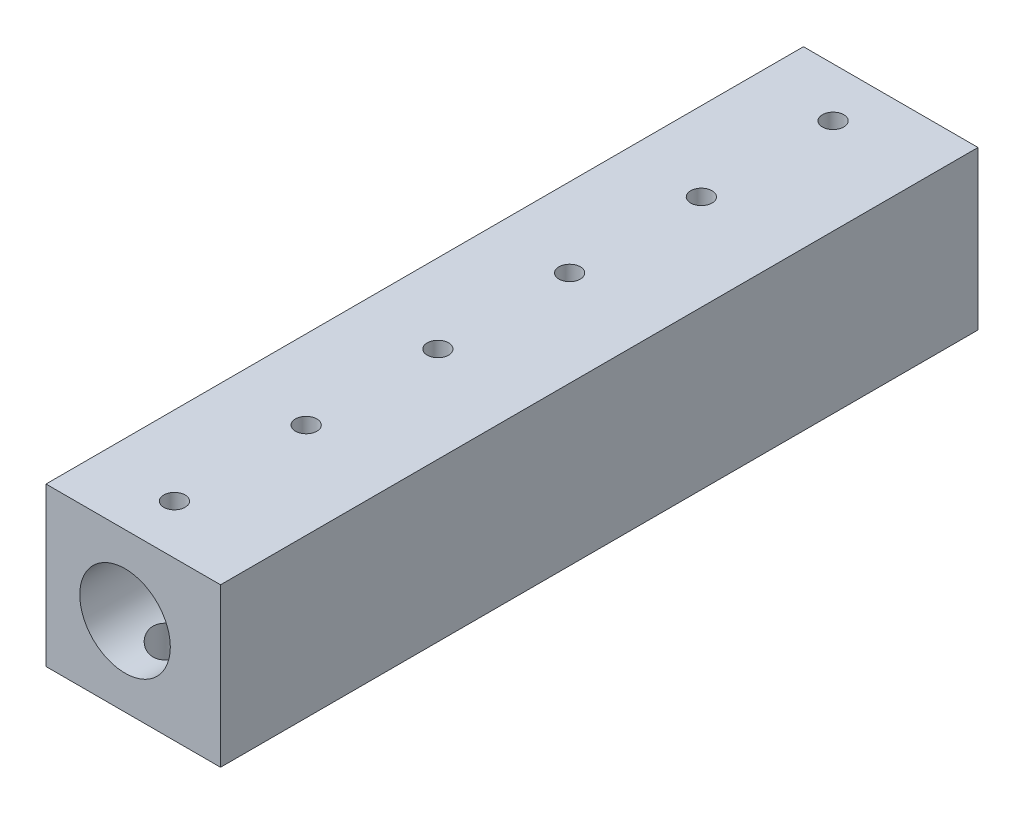
SolidWorks part; units mm, degrees
ref_plane "Front Plane" through (0, 0, 0) normal (0, 0, 1) x (1, 0, 0)
ref_plane "Top Plane" through (0, 0, 0) normal (0, 1, 0) x (1, 0, 0)
ref_plane "Right Plane" through (0, 0, 0) normal (1, 0, 0) x (0, 0, -1)
sketch "Sketch1" plane through (0, 0, 0) normal (0, 0, 1) x (1, 0, 0)
  line L1 (-24, -24) -> (24, -24)
  line L2 (-24, -24) -> (-24, 24)
  line L3 (-24, 24) -> (24, 24)
  line L4 (24, -24) -> (24, 24)
  line L5 (-24, -24) -> (24, 24) construction
  line L6 (-24, 24) -> (24, -24) construction
  line L7 (24, -24) -> (29, -24)
  line L8 (24, -24) -> (24, 35.2)
  line L9 (24, 35.2) -> (29, 35.2)
  line L10 (29, -24) -> (29, 35.2)
  line L11 (24, 35.2) -> (-24, 35.2)
  line L12 (24, 35.2) -> (24, 25.2)
  line L13 (24, 25.2) -> (-24, 25.2)
  line L14 (-24, 35.2) -> (-24, 25.2)
  circle A0 centre (0, 0) radius 13.75
  dimension "D1" = 27.5
  dimension "D2" = 1.2
  dimension "D3" = 48
  dimension "D4" = 48
  dimension "D5" = 5
  dimension "D6" = 10
extrude "Boss-Extrude1" add sketch "Sketch1" along normal blind 230 contours L1 L4 L3 L2 A0 | L11 L14 L13 L8 | L7 L10 L9 L8 L4 region at (-23.3212, 0, 0) region at (26.5, 5.6, 0) region at (0, 30.2, 0)
sketch "Sketch3" plane through (0, 35.2, 0) normal (0, 1, 0) x (1, 0, 0)
  line L0 (0, 0) -> (0, -230) construction
  line L1 (-24, -230) -> (29, -230) construction
  circle A0 centre (0, -15) radius 6
  circle A1 centre (0, -55) radius 6
  circle A2 centre (0, -95) radius 6
  circle A3 centre (0, -135) radius 6
  circle A4 centre (0, -175) radius 6
  circle A5 centre (0, -215) radius 6
  dimension "D1" = 12
  dimension "D2" = 15
  dimension "D4" = 15
  dimension "D3" = 6
extrude "Cut-Extrude1" cut sketch "Sketch3" against normal blind 0.5
sketch "Sketch4" plane through (0, 35.2, 0) normal (0, 1, 0) x (1, 0, 0)
  line L0 (0, 0) -> (0, -230) construction
  line L1 (-24, -230) -> (29, -230) construction
  circle A0 centre (0, -15) radius 3.25
  circle A1 centre (0, -55) radius 3.25
  circle A2 centre (0, -95) radius 3.25
  circle A3 centre (0, -135) radius 3.25
  circle A4 centre (0, -175) radius 3.25
  circle A5 centre (0, -215) radius 3.25
  dimension "D1" = 6.5
  dimension "D2" = 6
extrude "Cut-Extrude2" cut sketch "Sketch4" against normal through all
sketch "Sketch5" plane through (0, -24, 0) normal (0, -1, 0) x (1, 0, 0)
  line L0 (0, 230) -> (0, 0) construction
  line L1 (-24, 230) -> (29, 230) construction
  circle A0 centre (0, 215) radius 6.5
  circle A1 centre (0, 175) radius 6.5
  circle A2 centre (0, 135) radius 6.5
  circle A3 centre (0, 95) radius 6.5
  circle A4 centre (0, 55) radius 6.5
  circle A5 centre (0, 15) radius 6.5
  dimension "D1" = 13
  dimension "D2" = 6
extrude "Cut-Extrude3" cut sketch "Sketch5" against normal up to next
sketch "Sketch7" plane through (0, 24, 0) normal (0, 1, 0) x (1, 0, 0)
  line L0 (0, 0) -> (0, -230) construction
  line L1 (0, -8.5337) -> (-5.6, -11.7668)
  line L2 (-5.6, -11.7668) -> (-5.6, -18.2332)
  line L3 (-5.6, -18.2332) -> (0, -21.4663)
  line L4 (0, -21.4663) -> (5.6, -18.2332)
  line L5 (5.6, -18.2332) -> (5.6, -11.7668)
  line L6 (5.6, -11.7668) -> (0, -8.5337)
  line L7 (-24, -230) -> (29, -230) construction
  line L8 (0, -48.5337) -> (-5.6, -51.7668)
  line L9 (-5.6, -51.7668) -> (-5.6, -58.2332)
  line L10 (-5.6, -58.2332) -> (0, -61.4663)
  line L11 (0, -61.4663) -> (5.6, -58.2332)
  line L12 (5.6, -58.2332) -> (5.6, -51.7668)
  line L13 (5.6, -51.7668) -> (0, -48.5337)
  line L14 (0, -88.5337) -> (-5.6, -91.7668)
  line L15 (-5.6, -91.7668) -> (-5.6, -98.2332)
  line L16 (-5.6, -98.2332) -> (0, -101.4663)
  line L17 (0, -101.4663) -> (5.6, -98.2332)
  line L18 (5.6, -98.2332) -> (5.6, -91.7668)
  line L19 (5.6, -91.7668) -> (0, -88.5337)
  line L20 (0, -128.5337) -> (-5.6, -131.7668)
  line L21 (-5.6, -131.7668) -> (-5.6, -138.2332)
  line L22 (-5.6, -138.2332) -> (0, -141.4663)
  line L23 (0, -141.4663) -> (5.6, -138.2332)
  line L24 (5.6, -138.2332) -> (5.6, -131.7668)
  line L25 (5.6, -131.7668) -> (0, -128.5337)
  line L26 (0, -168.5337) -> (-5.6, -171.7668)
  line L27 (-5.6, -171.7668) -> (-5.6, -178.2332)
  line L28 (-5.6, -178.2332) -> (0, -181.4663)
  line L29 (0, -181.4663) -> (5.6, -178.2332)
  line L30 (5.6, -178.2332) -> (5.6, -171.7668)
  line L31 (5.6, -171.7668) -> (0, -168.5337)
  line L32 (0, -208.5337) -> (-5.6, -211.7668)
  line L33 (-5.6, -211.7668) -> (-5.6, -218.2332)
  line L34 (-5.6, -218.2332) -> (0, -221.4663)
  line L35 (0, -221.4663) -> (5.6, -218.2332)
  line L36 (5.6, -218.2332) -> (5.6, -211.7668)
  line L37 (5.6, -211.7668) -> (0, -208.5337)
  circle A0 centre (0, -15) radius 5.6 construction
  dimension "D1" = 11.2
  dimension "D2" = 6
extrude "Cut-Extrude4" cut sketch "Sketch7" against normal up to next from offset 5 offset against normal yes
chamfer "Chamfer1" distance 5 angle 45 6 edges at (0, 34.7, 218.25) (0, 34.7, 178.25) (0, 34.7, 138.25) (0, 34.7, 98.25) (0, 34.7, 58.25) (0, 34.7, 18.25)
sketch "Sketch8" plane through (24, 0, 0) normal (-1, 0, 0) x (0, 0, 1)
  line L1 (0, 25.2) -> (230, 25.2)
  line L2 (0, 25.2) -> (0, 24)
  line L3 (0, 24) -> (230, 24)
  line L4 (230, 25.2) -> (230, 24)
extrude "Cut-Extrude6" cut sketch "Sketch8" against normal blind 10
